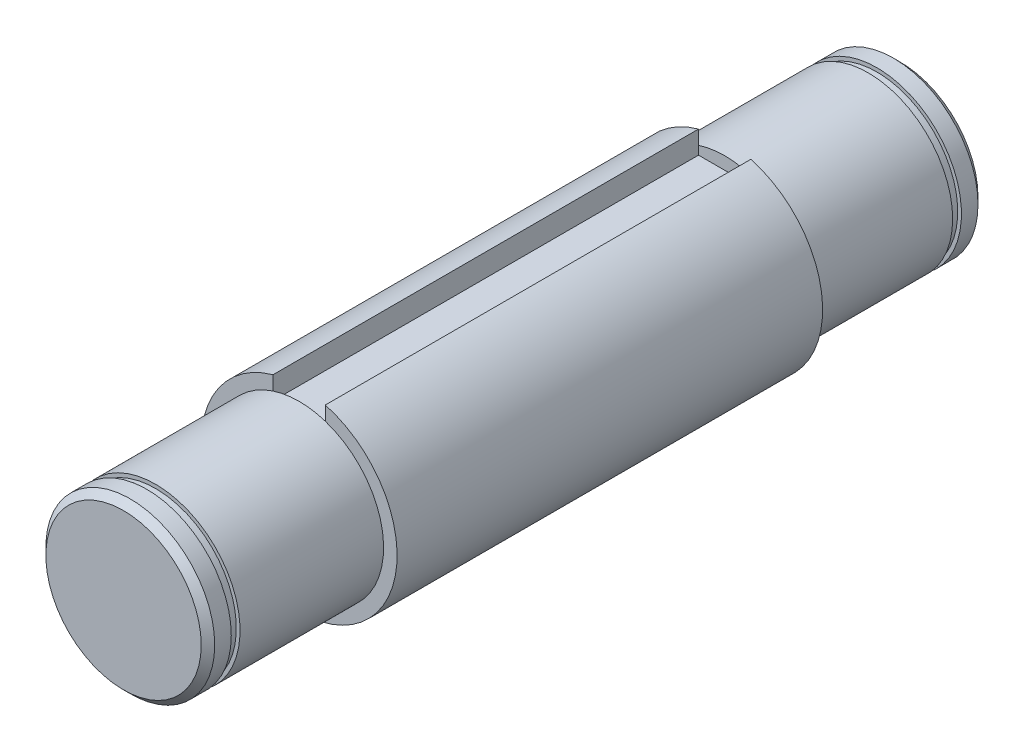
SolidWorks part; units mm, degrees
ref_plane "Front Plane" through (0, 0, 0) normal (0, 0, 1) x (1, 0, 0)
ref_plane "Top Plane" through (0, 0, 0) normal (0, 1, 0) x (1, 0, 0)
ref_plane "Right Plane" through (0, 0, 0) normal (1, 0, 0) x (0, 0, -1)
sketch "Sketch1" plane through (0, 0, 0) normal (0, 0, 1) x (1, 0, 0)
  circle A0 centre (0, 0) radius 12.5
  dimension "D1" = 25
extrude "Boss-Extrude1" add sketch "Sketch1" along normal blind 115
ref_plane "Plane1" through (0, 0, 57.5) normal (0, 0, -1) x (-1, 0, 0)
sketch "Sketch2" plane through (0, 0, 57.5) normal (0, 0, -1) x (-1, 0, 0)
  circle A0 centre (0, 0) radius 14.5
  dimension "D1" = 29
extrude "Boss-Extrude2" add sketch "Sketch2" along normal blind 31.5 and the other way blind 31.5
sketch "Sketch3" plane through (0, 0, 57.5) normal (0, 0, -1) x (-1, 0, 0)
  line L1 (-3.875, 18.375) -> (3.875, 18.375)
  line L2 (-3.875, 18.375) -> (-3.875, 10.625)
  line L3 (-3.875, 10.625) -> (3.875, 10.625)
  line L4 (3.875, 18.375) -> (3.875, 10.625)
  line L5 (-3.875, 18.375) -> (3.875, 10.625) construction
  line L6 (-3.875, 10.625) -> (3.875, 18.375) construction
  circle A0 centre (0, 0) radius 14.5 construction
  circle A1 centre (0, 0) radius 14.5 construction
  point P0 (0, 14.5)
  dimension "D1" = 7.75
  dimension "D2" = 7.75
extrude "Cut-Extrude1" cut sketch "Sketch3" against normal up to surface and the other way up to surface contours L4 L3 L2 L1 up to face at (-12.5, 0, 89) other way up to face at (-12.5, 0, 26)
sketch "Sketch4" plane through (0, 0, 0) normal (0, 1, 0) x (1, 0, 0)
  line L0 (-12.5, 0) -> (-12.5, -26) construction
  line L1 (-13.05, -3.45) -> (-11.95, -3.45)
  line L2 (-13.05, -3.45) -> (-13.05, -4.75)
  line L3 (-13.05, -4.75) -> (-11.95, -4.75)
  line L4 (-11.95, -3.45) -> (-11.95, -4.75)
  line L5 (-13.05, -3.45) -> (-11.95, -4.75) construction
  line L6 (-13.05, -4.75) -> (-11.95, -3.45) construction
  line L9 (0, 0) -> (0, -26) construction
  line L10 (-3.875, -26) -> (3.875, -26) construction
  line L12 (14.5, -57.5) -> (-14.5, -57.5) construction
  point P0 (-12.5, -4.1)
  dimension "D2" = 1.3
  dimension "D3" = 52.75
  dimension "D1" = 11.95
revolve "Cut-Revolve1" cut sketch "Sketch4" angle 360 about L9
mirror "Mirror1" about plane through (0, 0, 57.5) normal (0, 0, -1) of "Cut-Revolve1"
chamfer "Chamfer1" distance 1 angle 45 2 edges at (12.5, 0, 0) (12.5, 0, 115)
equation "\"large_shaft_diameter\"=29.00"
equation "\"small_shaft_diameter\"=25.00"
equation "\"length_shaft\"=115.00"
equation "\"large_length_shaft\"=31.50"
equation "\"width_key\"=7.75"
equation "\"D1@Sketch1\"=\"small_shaft_diameter\""
equation "\"D1@Boss-Extrude1\"=\"length_shaft\""
equation "\"D1@Sketch2\"=\"large_shaft_diameter\""
equation "\"D1@Boss-Extrude2\"=\"large_length_shaft\""
equation "\"D2@Boss-Extrude2\"=\"large_length_shaft\""
equation "\"D2@Sketch3\"=\"width_key\""
equation "\"D1@Sketch3\"=\"width_key\""
equation "\"snap_ring_location\"=52.75"
equation "\"snap_ring_groove_radius\"=11.95"
equation "\"snap_ring_groove_width\"=1.30"
equation "\"D3@Sketch4\"=\"snap_ring_location\""
equation "\"D2@Sketch4\"=\"snap_ring_groove_width\""
equation "\"D1@Sketch4\"=\"snap_ring_groove_radius\""
